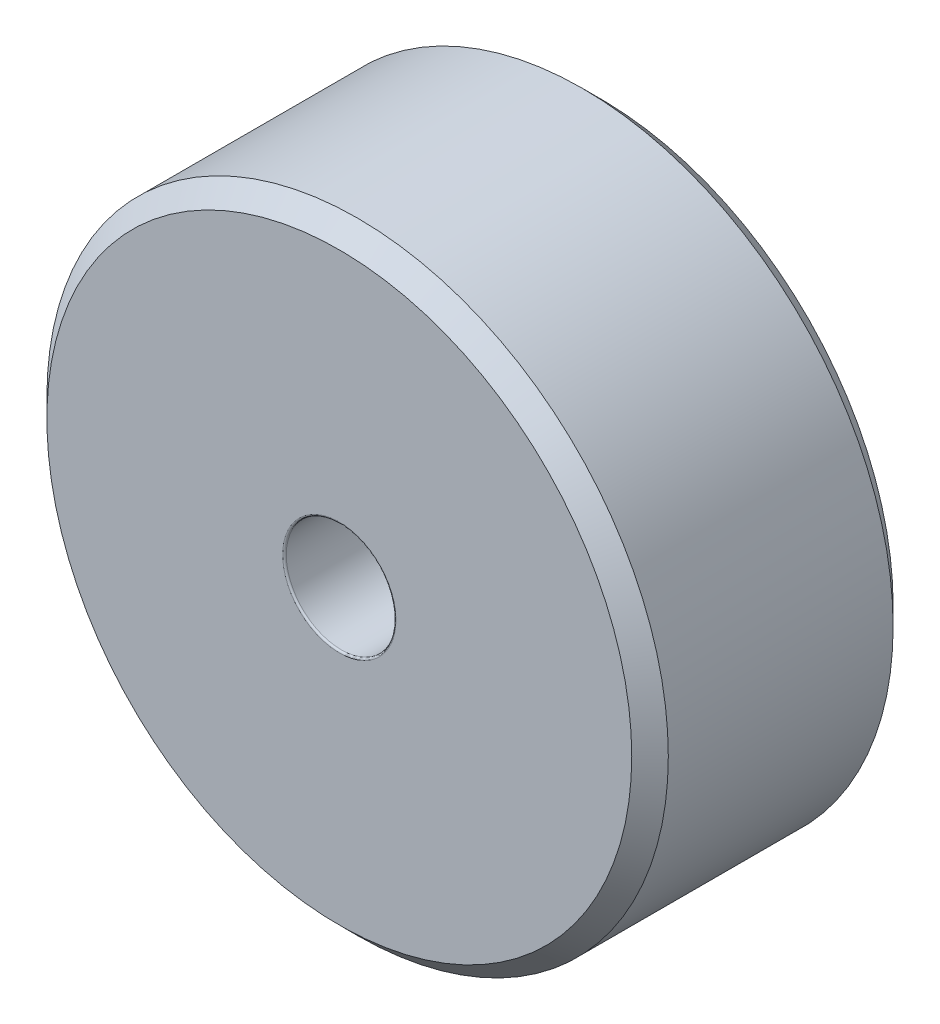
SolidWorks part; units mm, degrees
ref_plane "前视基准面" through (0, 0, 0) normal (0, 0, 1) x (1, 0, 0)
ref_plane "上视基准面" through (0, 0, 0) normal (0, 1, 0) x (1, 0, 0)
ref_plane "右视基准面" through (0, 0, 0) normal (1, 0, 0) x (0, 0, -1)
other "Configuration Table"
sketch "草图1" plane through (0, 0, 0) normal (0, 0, 1) x (1, 0, 0)
  circle A0 centre (0, 0) radius 17
  circle A1 centre (0, 0) radius 3
  dimension "D1" = 34
  dimension "D2" = 6
extrude "凸台-拉伸1" add sketch "草图1" along normal blind 14.3
sketch "草图2" plane through (0, 0, 0) normal (0, 0, -1) x (-1, 0, 0)
  circle A0 centre (0, 0) radius 4.25
  circle A1 centre (0, 0) radius 3
  dimension "D1" = 6
  dimension "D2" = 8.5
extrude "凸台-拉伸2" add sketch "草图2" along normal blind 0.7
chamfer "倒角1" distance 1 angle 45 2 edges at (17, 0, 0) (17, 0, 14.3)
fillet "圆角1" radius 0.1 3 edges at (3, 0, 14.3) (-3, 0, -0.7) (-4.25, 0, -0.7)
